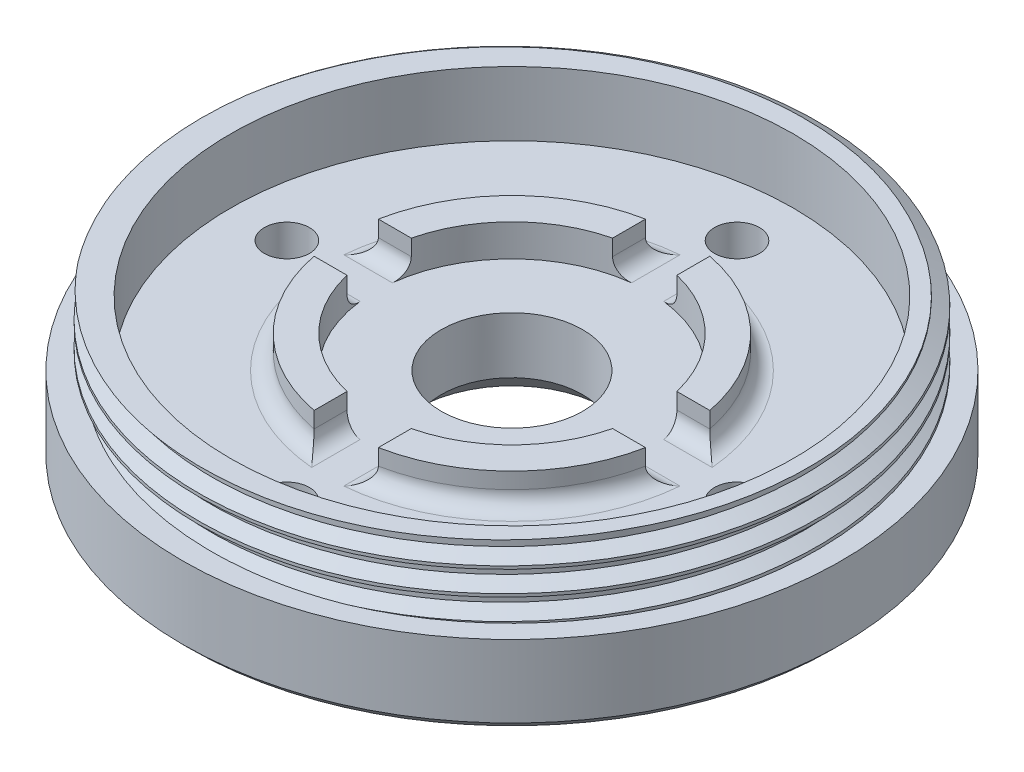
SolidWorks part; units mm, degrees
ref_plane "Front plane" through (0, 0, 0) normal (0, 0, 1) x (1, 0, 0)
ref_plane "Top plane" through (0, 0, 0) normal (0, 1, 0) x (1, 0, 0)
ref_plane "Right plane" through (0, 0, 0) normal (1, 0, 0) x (0, 0, -1)
ref_axis "Axis X" through (0, 0, 0) along (1, 0, 0)
ref_axis "Axis Y" through (0, 0, 0) along (0, 1, 0)
ref_axis "Axis Z" through (0, 0, 0) along (0, 0, 1)
sketch "Sketch1" plane through (0, 0, 0) normal (0, 1, 0) x (1, 0, 0)
  circle A0 centre (0, 0) radius 20.5
  circle A1 centre (0, 0) radius 4.4
  circle A2 centre (0, 0) radius 14 construction
  circle A3 centre (0, 14) radius 1.4
  circle A4 centre (14, 0) radius 1.4
  circle A5 centre (0, -14) radius 1.4
  circle A6 centre (-14, 0) radius 1.4
  point P16 (0, 0)
  dimension "D1" = 41
  dimension "D2" = 8.8
  dimension "D3" = 28
  dimension "D4" = 2.8
  dimension "D5" = 4
extrude "Extrude1" add sketch "Sketch1" along normal blind 5
sketch "Sketch8" plane through (0, 5, 0) normal (0, 1, 0) x (1, 0, 0)
  circle A1 centre (0, 0) radius 17.5
  circle A3 centre (0, 0) radius 18.45
  dimension "D1" = 35
  dimension "D2" = 0.95
extrude "Бобышка-Вытянуть1" add sketch "Sketch8" along normal blind 4
thread "Резьба1" pitch 1.5 method extrude trim with start face yes trim with end face yes profile "Профиль резьбы1" start angle 0, offset 2, length 0, pitch 1.5, diameter 36.9
ref_plane "Плоскость1" through (-18.45, 11, 0) normal (0, 0, 1) x (-1, 0, 0)
sketch "Профиль резьбы1" plane through (-18.45, 11, 0) normal (0, 0, 1) x (-1, 0, 0)
  line L0 (0, 0) -> (0, 1.5) construction
  line L1 (0, 0) -> (0.8119, 0.4687)
  line L2 (0.8119, 0.4687) -> (0.8119, 0.6562)
  line L3 (0.8119, 0.6562) -> (0, 1.125)
  line L4 (0.8119, 0.5625) -> (0, 0.5625) construction
  line L11 (0, 0) -> (0, 1.125)
  point P2 (0, 0)
  dimension "Pitch" = 1.5
  dimension "Profile_Angle" = 60
  dimension "Profile_Land" = 0.1875
  dimension "Profile_Height" = 0.8119
sketch "Эскиз3" plane through (0, 5, 0) normal (0, 1, 0) x (1, 0, 0)
  line L0 (0, 0) -> (0, 10) construction
  line L1 (-2, 10.3078) -> (-2, 8.2614)
  line L2 (2, 10.3078) -> (2, 8.2614)
  line L3 (10.3078, 2) -> (8.2614, 2)
  line L4 (10.3078, -2) -> (8.2614, -2)
  line L5 (2, -10.3078) -> (2, -8.2614)
  line L6 (-2, -10.3078) -> (-2, -8.2614)
  line L7 (-10.3078, -2) -> (-8.2614, -2)
  line L8 (-10.3078, 2) -> (-8.2614, 2)
  arc A0 (-2, 8.2614) -> (-8.2614, 2) centre (0, 0) ccw
  arc A1 (-2, 10.3078) -> (-10.3078, 2) centre (0, 0) ccw
  arc A2 (8.2614, 2) -> (2, 8.2614) centre (0, 0) ccw
  arc A3 (10.3078, 2) -> (2, 10.3078) centre (0, 0) ccw
  arc A4 (-8.2614, -2) -> (-2, -8.2614) centre (0, 0) ccw
  arc A5 (-10.3078, -2) -> (-2, -10.3078) centre (0, 0) ccw
  arc A6 (2, -8.2614) -> (8.2614, -2) centre (0, 0) ccw
  arc A7 (2, -10.3078) -> (10.3078, -2) centre (0, 0) ccw
  dimension "D1" = 17
  dimension "D2" = 2
  dimension "D3" = 4
  dimension "D4" = 4
extrude "Бобышка-Вытянуть2" add sketch "Эскиз3" along normal blind 2
fillet "Скругление1" radius 1 12 edges at (-2, 5, -9.2846) (2, 5, -9.2846) (7.4246, 5, -7.4246) (9.2846, 5, -2) (9.2846, 5, 2) (7.4246, 5, 7.4246) (-7.4246, 5, -7.4246) (-7.4246, 5, 7.4246) (2, 5, 9.2846) (-2, 5, 9.2846) (-9.2846, 5, 2) (-9.2846, 5, -2)
chamfer "Chamfer2" distance 1.5 angle 45 1 edges at (0, 0, 4.4)
chamfer "Chamfer3" distance 0.5 angle 45 1 edges at (0, 0, 20.5)
chamfer "Chamfer4" distance 1 angle 45 4 edges at (0, 0, -12.6) (14, 0, 1.4) (-14, 0, 1.4) (0, 0, 15.4)
equation "\"D1@Sketch1\" = \"module_diameter\""
equation "\"D2@Sketch1\" = 9.8 - 1"
equation "\"D4@Sketch1\"=3-\"print_offset\""
equation "\"D1@Sketch8\"= \"module_diameter\" - 6"
equation "\"D2@Sketch8\"= 0.95"
equation "\"D1@Эскиз3\"=\"bearing_d2\""
equation "\"D1@Бобышка-Вытянуть2\"=\"bearing h\"/3"
equation "\"bearing_d1\"= 6'Bearing inner diameter"
equation "\"bearing_d2\"= 17'Bearing external diameter"
equation "\"bearing h\"= 6'Bearing heigh"
equation "\"pin_d\"= 2'Pin diameter"
equation "\"pin_h\"= 12'Pin heigh"
equation "\"print_offset\"= 0.2'Offset for printing holes"
equation "\"module_diameter\"= 41"
